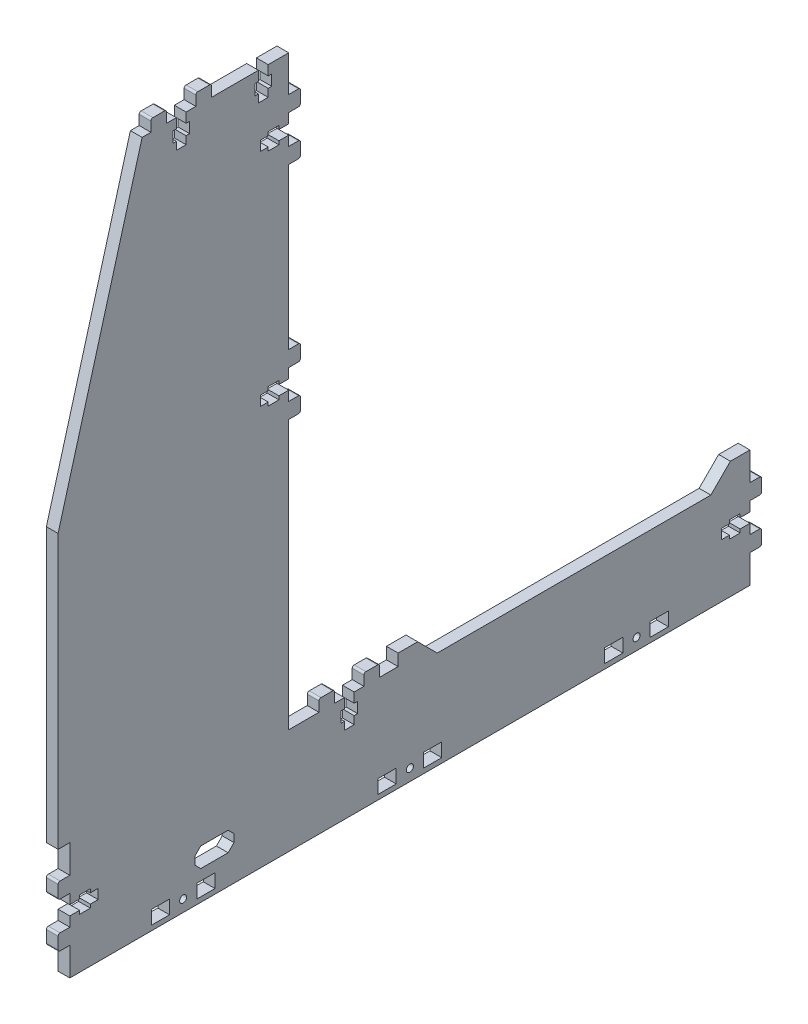
SolidWorks part; units mm, degrees
ref_plane "Plan de face" through (0, 0, 0) normal (0, 0, 1) x (1, 0, 0)
ref_plane "Plan de dessus" through (0, 0, 0) normal (0, 1, 0) x (1, 0, 0)
ref_plane "Plan de droite" through (0, 0, 0) normal (1, 0, 0) x (0, 0, -1)
sketch "Esquisse2" plane through (0, 0, 0) normal (1, 0, 0) x (0, 0, -1)
  line L0 (-180, 200) -> (-180, 60)
  line L1 (-180, 200) -> (-137, 354)
  line L2 (-137, 354) -> (-62, 354)
  line L3 (-62, 354) -> (-62, 54)
  line L4 (-62, 54) -> (-6, 54)
  line L5 (-6, 54) -> (-6, 60)
  line L6 (-6, 60) -> (4, 60)
  line L7 (4, 60) -> (14, 50)
  line L8 (14, 50) -> (154, 50)
  line L9 (154, 50) -> (164, 60)
  line L10 (164, 60) -> (174, 60)
  line L11 (174, 60) -> (174, 0)
  line L12 (174, 0) -> (-174, 0)
  line L13 (4, 60) -> (119.7586, 60) construction
  line L14 (-180, 60) -> (-174, 60)
  line L15 (-62, 204) -> (0, 204) construction
  line L16 (-174, 60) -> (-174, 0)
  line L17 (0, 0) -> (0, 204) construction
  line L18 (-174, 6) -> (174, 6) construction
  point P2 (0, 0)
  point P18 (-62, 204)
  line B0 (-132.3, 9.5) -> (-123, 9.5)
  line B1 (-132.3, 9.5) -> (-132.3, 2.5)
  line B2 (-132.3, 2.5) -> (-123, 2.5)
  line B3 (-123, 9.5) -> (-123, 2.5)
  line B4 (-109, 9.5) -> (-109, 2.5)
  line B5 (-99.7, 2.5) -> (-109, 2.5)
  line B6 (-99.7, 9.5) -> (-99.7, 2.5)
  line B7 (-99.7, 9.5) -> (-109, 9.5)
  circle B8 centre (-116, 6) radius 1.8
  line B9 (-16.3, 9.5) -> (-7, 9.5)
  line B10 (-16.3, 9.5) -> (-16.3, 2.5)
  line B11 (-16.3, 2.5) -> (-7, 2.5)
  line B12 (-7, 9.5) -> (-7, 2.5)
  line B13 (7, 9.5) -> (7, 2.5)
  line B14 (16.3, 2.5) -> (7, 2.5)
  line B15 (16.3, 9.5) -> (16.3, 2.5)
  line B16 (16.3, 9.5) -> (7, 9.5)
  circle B17 centre (0, 6) radius 1.8
  line B18 (132.3, 2.5) -> (123, 2.5)
  line B19 (132.3, 2.5) -> (132.3, 9.5)
  line B20 (132.3, 9.5) -> (123, 9.5)
  line B21 (123, 2.5) -> (123, 9.5)
  line B22 (109, 2.5) -> (109, 9.5)
  line B23 (99.7, 9.5) -> (109, 9.5)
  line B24 (99.7, 2.5) -> (99.7, 9.5)
  line B25 (99.7, 2.5) -> (109, 2.5)
  circle B26 centre (116, 6) radius 1.8
  dimension "D1" = 348
  dimension "D2" = 354
  dimension "D3" = 75
  dimension "D4" = 62
  dimension "D5" = 56
  dimension "D6" = 6
  dimension "D7" = 10
  dimension "D8" = 10
  dimension "D9" = 118
  dimension "D10" = 45
  dimension "D11" = 10
  dimension "D12" = 60
  dimension "D14" = 6
  dimension "D15" = 58
  dimension "s" = 200
  dimension "D16" = 58
sketch_block_instance "attache_femelle-1"
sketch_block "attache_femelle" parameters "D1"=3.6, "D2"=9.3, "D3"=7, "D4"=7
sketch_block_instance "attache_femelle-2"
sketch_block_instance "attache_femelle-5"
extrude "Boss.-Extru.1" add sketch "Esquisse2" along normal mid plane 6
sketch "Esquisse4" plane through (3, 0, 0) normal (1, 0, 0) x (0, 0, -1)
  line L0 (174, 30) -> (-174, 30) construction
  line L1 (-62, 54) -> (-62, 360) construction
  line L2 (-6, 54) -> (-56, 54) construction
  line L3 (-174, 0) -> (174, 0) construction
  line L8 (174, 0) -> (174, 60) construction
  line L10 (-62, 54) -> (-62, 354) construction
  line L11 (-6, 54) -> (-62, 54) construction
  line L12 (-174, 60) -> (-174, 0) construction
  line L13 (-62, 354) -> (-137, 354) construction
  line B0 (-174, 14.5) -> (-179, 14.5)
  line B1 (-180, 15.5) -> (-180, 21.5)
  line B2 (-179, 22.5) -> (-174, 22.5)
  line B3 (-174, 22.5) -> (-174, 27.5)
  line B4 (-174, 27.5) -> (-169, 27.5)
  line B5 (-169, 27.5) -> (-169, 25.7)
  line B6 (-169, 25.7) -> (-163.5, 25.7)
  line B7 (-163.5, 25.7) -> (-163.5, 27.5)
  line B8 (-163.5, 27.5) -> (-159.5, 27.5)
  line B9 (-159.5, 27.5) -> (-159.5, 32.5)
  line B10 (-159.5, 30) -> (-174, 30) construction
  line B11 (-174, 45.5) -> (-174, 37.5)
  line B12 (-174, 22.5) -> (-174, 14.5)
  line B13 (-163.5, 32.5) -> (-159.5, 32.5)
  line B14 (-163.5, 34.3) -> (-163.5, 32.5)
  line B15 (-169, 34.3) -> (-163.5, 34.3)
  line B16 (-169, 32.5) -> (-169, 34.3)
  line B17 (-174, 32.5) -> (-169, 32.5)
  line B18 (-174, 37.5) -> (-174, 32.5)
  line B19 (-179, 37.5) -> (-174, 37.5)
  line B20 (-180, 44.5) -> (-180, 38.5)
  line B21 (-174, 45.5) -> (-179, 45.5)
  line B22 (-174, 27.5) -> (-174, 32.5)
  arc B23 (-180, 21.5) -> (-179, 22.5) centre (-179, 21.5) cw
  arc B24 (-179, 14.5) -> (-180, 15.5) centre (-179, 15.5) cw
  arc B25 (-179, 45.5) -> (-180, 44.5) centre (-179, 44.5) ccw
  arc B26 (-180, 38.5) -> (-179, 37.5) centre (-179, 38.5) ccw
  line B27 (174, 45.5) -> (179, 45.5)
  line B28 (180, 44.5) -> (180, 38.5)
  line B29 (179, 37.5) -> (174, 37.5)
  line B30 (174, 37.5) -> (174, 32.5)
  line B31 (174, 32.5) -> (169, 32.5)
  line B32 (169, 32.5) -> (169, 34.3)
  line B33 (169, 34.3) -> (163.5, 34.3)
  line B34 (163.5, 34.3) -> (163.5, 32.5)
  line B35 (163.5, 32.5) -> (159.5, 32.5)
  line B36 (159.5, 32.5) -> (159.5, 27.5)
  line B37 (159.5, 30) -> (174, 30) construction
  line B38 (174, 14.5) -> (174, 22.5)
  line B39 (174, 37.5) -> (174, 45.5)
  line B40 (163.5, 27.5) -> (159.5, 27.5)
  line B41 (163.5, 25.7) -> (163.5, 27.5)
  line B42 (169, 25.7) -> (163.5, 25.7)
  line B43 (169, 27.5) -> (169, 25.7)
  line B44 (174, 27.5) -> (169, 27.5)
  line B45 (174, 22.5) -> (174, 27.5)
  line B46 (179, 22.5) -> (174, 22.5)
  line B47 (180, 15.5) -> (180, 21.5)
  line B48 (174, 14.5) -> (179, 14.5)
  line B49 (174, 32.5) -> (174, 27.5)
  arc B50 (180, 38.5) -> (179, 37.5) centre (179, 38.5) cw
  arc B51 (179, 45.5) -> (180, 44.5) centre (179, 44.5) cw
  arc B52 (179, 14.5) -> (180, 15.5) centre (179, 15.5) ccw
  arc B53 (180, 21.5) -> (179, 22.5) centre (179, 21.5) ccw
  line B54 (-46.5, 54) -> (-46.5, 59)
  line B55 (-45.5, 60) -> (-39.5, 60)
  line B56 (-38.5, 59) -> (-38.5, 54)
  line B57 (-38.5, 54) -> (-33.5, 54)
  line B58 (-33.5, 54) -> (-33.5, 49)
  line B59 (-33.5, 49) -> (-35.3, 49)
  line B60 (-35.3, 49) -> (-35.3, 43.5)
  line B61 (-35.3, 43.5) -> (-33.5, 43.5)
  line B62 (-33.5, 43.5) -> (-33.5, 39.5)
  line B63 (-33.5, 39.5) -> (-28.5, 39.5)
  line B64 (-31, 39.5) -> (-31, 54) construction
  line B65 (-15.5, 54) -> (-23.5, 54)
  line B66 (-38.5, 54) -> (-46.5, 54)
  line B67 (-28.5, 43.5) -> (-28.5, 39.5)
  line B68 (-26.7, 43.5) -> (-28.5, 43.5)
  line B69 (-26.7, 49) -> (-26.7, 43.5)
  line B70 (-28.5, 49) -> (-26.7, 49)
  line B71 (-28.5, 54) -> (-28.5, 49)
  line B72 (-23.5, 54) -> (-28.5, 54)
  line B73 (-23.5, 59) -> (-23.5, 54)
  line B74 (-16.5, 60) -> (-22.5, 60)
  line B75 (-15.5, 54) -> (-15.5, 59)
  line B76 (-33.5, 54) -> (-28.5, 54)
  arc B77 (-39.5, 60) -> (-38.5, 59) centre (-39.5, 59) cw
  arc B78 (-46.5, 59) -> (-45.5, 60) centre (-45.5, 59) cw
  arc B79 (-15.5, 59) -> (-16.5, 60) centre (-16.5, 59) ccw
  arc B80 (-22.5, 60) -> (-23.5, 59) centre (-22.5, 59) ccw
  line B81 (-62, 222.5) -> (-57, 222.5)
  line B82 (-56, 221.5) -> (-56, 215.5)
  line B83 (-57, 214.5) -> (-62, 214.5)
  line B84 (-62, 214.5) -> (-62, 209.5)
  line B85 (-62, 209.5) -> (-67, 209.5)
  line B86 (-67, 209.5) -> (-67, 211.3)
  line B87 (-67, 211.3) -> (-72.5, 211.3)
  line B88 (-72.5, 211.3) -> (-72.5, 209.5)
  line B89 (-72.5, 209.5) -> (-76.5, 209.5)
  line B90 (-76.5, 209.5) -> (-76.5, 204.5)
  line B91 (-76.5, 207) -> (-62, 207) construction
  line B92 (-62, 191.5) -> (-62, 199.5)
  line B93 (-62, 214.5) -> (-62, 222.5)
  line B94 (-72.5, 204.5) -> (-76.5, 204.5)
  line B95 (-72.5, 202.7) -> (-72.5, 204.5)
  line B96 (-67, 202.7) -> (-72.5, 202.7)
  line B97 (-67, 204.5) -> (-67, 202.7)
  line B98 (-62, 204.5) -> (-67, 204.5)
  line B99 (-62, 199.5) -> (-62, 204.5)
  line B100 (-57, 199.5) -> (-62, 199.5)
  line B101 (-56, 192.5) -> (-56, 198.5)
  line B102 (-62, 191.5) -> (-57, 191.5)
  line B103 (-62, 209.5) -> (-62, 204.5)
  arc B104 (-56, 215.5) -> (-57, 214.5) centre (-57, 215.5) cw
  arc B105 (-57, 222.5) -> (-56, 221.5) centre (-57, 221.5) cw
  arc B106 (-57, 191.5) -> (-56, 192.5) centre (-57, 192.5) ccw
  arc B107 (-56, 198.5) -> (-57, 199.5) centre (-57, 198.5) ccw
  line B108 (-62, 335.5) -> (-57, 335.5)
  line B109 (-56, 334.5) -> (-56, 328.5)
  line B110 (-57, 327.5) -> (-62, 327.5)
  line B111 (-62, 327.5) -> (-62, 322.5)
  line B112 (-62, 322.5) -> (-67, 322.5)
  line B113 (-67, 322.5) -> (-67, 324.3)
  line B114 (-67, 324.3) -> (-72.5, 324.3)
  line B115 (-72.5, 324.3) -> (-72.5, 322.5)
  line B116 (-72.5, 322.5) -> (-76.5, 322.5)
  line B117 (-76.5, 322.5) -> (-76.5, 317.5)
  line B118 (-76.5, 320) -> (-62, 320) construction
  line B119 (-62, 304.5) -> (-62, 312.5)
  line B120 (-62, 327.5) -> (-62, 335.5)
  line B121 (-72.5, 317.5) -> (-76.5, 317.5)
  line B122 (-72.5, 315.7) -> (-72.5, 317.5)
  line B123 (-67, 315.7) -> (-72.5, 315.7)
  line B124 (-67, 317.5) -> (-67, 315.7)
  line B125 (-62, 317.5) -> (-67, 317.5)
  line B126 (-62, 312.5) -> (-62, 317.5)
  line B127 (-57, 312.5) -> (-62, 312.5)
  line B128 (-56, 305.5) -> (-56, 311.5)
  line B129 (-62, 304.5) -> (-57, 304.5)
  line B130 (-62, 322.5) -> (-62, 317.5)
  arc B131 (-56, 328.5) -> (-57, 327.5) centre (-57, 328.5) cw
  arc B132 (-57, 335.5) -> (-56, 334.5) centre (-57, 334.5) cw
  arc B133 (-57, 304.5) -> (-56, 305.5) centre (-57, 305.5) ccw
  arc B134 (-56, 311.5) -> (-57, 312.5) centre (-57, 311.5) ccw
  line B135 (-90.5, 354) -> (-90.5, 359)
  line B136 (-89.5, 360) -> (-83.5, 360)
  line B137 (-82.5, 359) -> (-82.5, 354)
  line B138 (-82.5, 354) -> (-77.5, 354)
  line B139 (-77.5, 354) -> (-77.5, 349)
  line B140 (-77.5, 349) -> (-79.3, 349)
  line B141 (-79.3, 349) -> (-79.3, 343.5)
  line B142 (-79.3, 343.5) -> (-77.5, 343.5)
  line B143 (-77.5, 343.5) -> (-77.5, 339.5)
  line B144 (-77.5, 339.5) -> (-72.5, 339.5)
  line B145 (-75, 339.5) -> (-75, 354) construction
  line B146 (-59.5, 354) -> (-67.5, 354)
  line B147 (-82.5, 354) -> (-90.5, 354)
  line B148 (-72.5, 343.5) -> (-72.5, 339.5)
  line B149 (-70.7, 343.5) -> (-72.5, 343.5)
  line B150 (-70.7, 349) -> (-70.7, 343.5)
  line B151 (-72.5, 349) -> (-70.7, 349)
  line B152 (-72.5, 354) -> (-72.5, 349)
  line B153 (-67.5, 354) -> (-72.5, 354)
  line B154 (-67.5, 359) -> (-67.5, 354)
  line B155 (-60.5, 360) -> (-66.5, 360)
  line B156 (-59.5, 354) -> (-59.5, 359)
  line B157 (-77.5, 354) -> (-72.5, 354)
  arc B158 (-83.5, 360) -> (-82.5, 359) centre (-83.5, 359) cw
  arc B159 (-90.5, 359) -> (-89.5, 360) centre (-89.5, 359) cw
  arc B160 (-59.5, 359) -> (-60.5, 360) centre (-60.5, 359) ccw
  arc B161 (-66.5, 360) -> (-67.5, 359) centre (-66.5, 359) ccw
  line B162 (-132.5, 354) -> (-132.5, 359)
  line B163 (-131.5, 360) -> (-125.5, 360)
  line B164 (-124.5, 359) -> (-124.5, 354)
  line B165 (-124.5, 354) -> (-119.5, 354)
  line B166 (-119.5, 354) -> (-119.5, 349)
  line B167 (-119.5, 349) -> (-121.3, 349)
  line B168 (-121.3, 349) -> (-121.3, 343.5)
  line B169 (-121.3, 343.5) -> (-119.5, 343.5)
  line B170 (-119.5, 343.5) -> (-119.5, 339.5)
  line B171 (-119.5, 339.5) -> (-114.5, 339.5)
  line B172 (-117, 339.5) -> (-117, 354) construction
  line B173 (-101.5, 354) -> (-109.5, 354)
  line B174 (-124.5, 354) -> (-132.5, 354)
  line B175 (-114.5, 343.5) -> (-114.5, 339.5)
  line B176 (-112.7, 343.5) -> (-114.5, 343.5)
  line B177 (-112.7, 349) -> (-112.7, 343.5)
  line B178 (-114.5, 349) -> (-112.7, 349)
  line B179 (-114.5, 354) -> (-114.5, 349)
  line B180 (-109.5, 354) -> (-114.5, 354)
  line B181 (-109.5, 359) -> (-109.5, 354)
  line B182 (-102.5, 360) -> (-108.5, 360)
  line B183 (-101.5, 354) -> (-101.5, 359)
  line B184 (-119.5, 354) -> (-114.5, 354)
  arc B185 (-125.5, 360) -> (-124.5, 359) centre (-125.5, 359) cw
  arc B186 (-132.5, 359) -> (-131.5, 360) centre (-131.5, 359) cw
  arc B187 (-101.5, 359) -> (-102.5, 360) centre (-102.5, 359) ccw
  arc B188 (-108.5, 360) -> (-109.5, 359) centre (-108.5, 359) ccw
  line B189 (-110, 22) -> (-107, 25)
  line B190 (-107, 15) -> (-93, 15)
  line B191 (-110, 18) -> (-110, 22)
  line B192 (-107, 25) -> (-93, 25)
  line B193 (-90, 18) -> (-90, 22)
  line B194 (-110, 15) -> (-90, 25) construction
  line B195 (-110, 25) -> (-90, 15) construction
  line B196 (-93, 25) -> (-90, 22)
  line B197 (-93, 15) -> (-90, 18)
  line B198 (-110, 18) -> (-107, 15)
  dimension "D1" = 20
  dimension "D2" = 13
  dimension "D3" = 34
  dimension "D4" = 6
  dimension "D5" = 6
  dimension "D6" = 100
  dimension "D7" = 20
sketch_block_instance "attache_male-1"
sketch_block "attache_male" parameters "D7"=1, "D1"=5, "D2"=5, "D3"=5.5, "D4"=1.8, "D5"=4, "D6"=2.5
sketch_block_instance "attache_male-2"
sketch_block_instance "attache_male-3"
sketch_block_instance "attache_male-4"
sketch_block_instance "attache_male-5"
sketch_block_instance "attache_male-6"
sketch_block_instance "attache_male-7"
sketch_block_instance "cable_hole-1"
sketch_block "cable_hole" parameters "D1"=20, "D2"=10
extrude "Boss.-Extru.2" add sketch "Esquisse4" against normal blind 6 contours B186 B162 B164 B185 B163 | B182 B188 B181 B183 B187 | B132 B108 B110 B131 B109 | B128 B134 B127 B129 B133 | B105 B81 B83 B104 B82 | B101 B107 B100 B102 B106 | B20 B26 B19 B21 B25 | B24 B0 B2 B23 B1 | B78 B54 B56 B77 B55 | B74 B80 B73 B75 B79 | B51 B27 B29 B50 B28 | B47 B53 B46 B48 B52 region at (3, 41.5, 176.9749) region at (3, 18.5, 176.9749) region at (3, 18.5, -176.9749) region at (3, 41.5, -176.9749) region at (3, 56.9749, 19.5) region at (3, 56.9749, 42.5) region at (3, 195.5, 59.0251) region at (3, 218.5, 59.0251) region at (3, 308.5, 59.0251) region at (3, 331.5, 59.0251) region at (3, 356.9749, 105.5) region at (3, 356.9749, 128.5)
extrude "Enlèv. mat.-Extru.1" cut sketch "Esquisse4<3>" against normal blind 6 contours B179 B166 B167 B168 B169 B170 B171 B175 B176 B177 B178 | B152 B139 B140 B141 B142 B143 B144 B148 B149 B150 B151 | B125 B112 B113 B114 B115 B116 B117 B121 B122 B123 B124 | B98 B85 B86 B87 B88 B89 B90 B94 B95 B96 B97 | B71 B58 B59 B60 B61 B62 B63 B67 B68 B69 B70 | B22 B4 B5 B6 B7 B8 B9 | B9 B13 B14 B15 B16 B17 | B36 B49 B31 B32 B33 B34 B35 | B36 B40 B41 B42 B43 B44 | B191 B198 B190 B197 B193 B196 B192 B189 region at (3, 30, 166.6427) region at (3, 30, -166.6427) region at (3, 46.6427, 31) region at (3, 207, 69.3573) region at (3, 320, 69.3573) region at (3, 346.6427, 75) region at (3, 346.6427, 117) region at (3, 20, 100)
sketch "Esquisse4<3>" plane through (3, 0, 0) normal (1, 0, 0) x (0, 0, -1) same geometry as "Esquisse4"
equation "\"L\"= \"L@Prusa i4.2.sldasm\""
equation "\"H\"= \"H@Prusa i4.2.sldasm\""
equation "\"D1@Esquisse2\"=\"L\""
equation "\"D2@Esquisse2\"=\"H\"-6"
equation "\"s\"=175"
equation "\"D16@Esquisse2\"=\"L\"/6"
equation "\"D15@Esquisse2\"=\"L\"/6"
